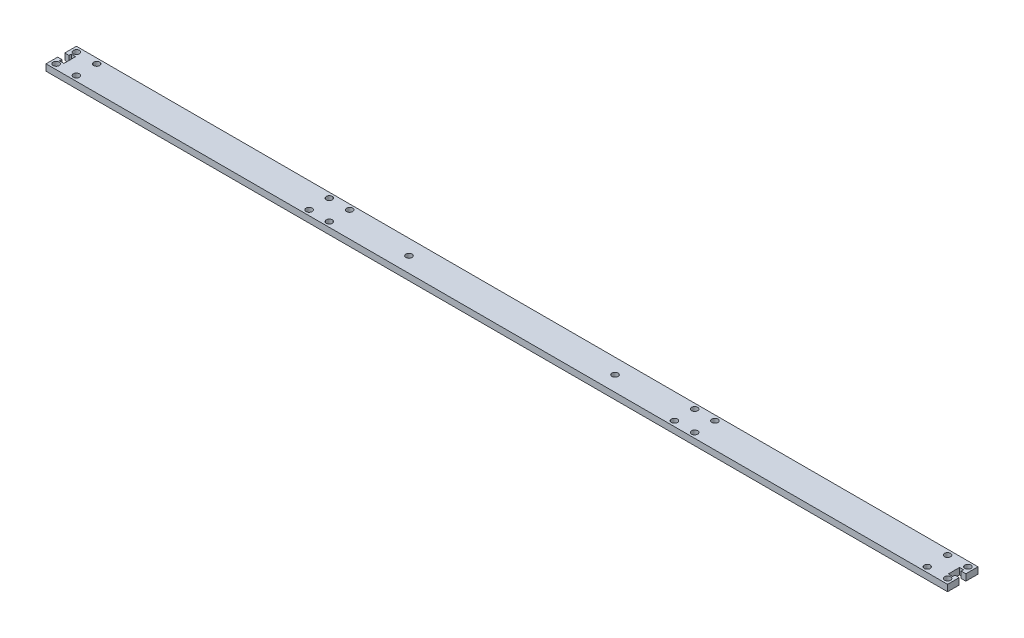
SolidWorks part; units mm, degrees
ref_plane "Front Plane" through (0, 0, 0) normal (0, 0, 1) x (1, 0, 0)
ref_plane "Top Plane" through (0, 0, 0) normal (0, 1, 0) x (1, 0, 0)
ref_plane "Right Plane" through (0, 0, 0) normal (1, 0, 0) x (0, 0, -1)
sketch "Sketch1" plane through (0, 0, 0) normal (0, 1, 0) x (1, 0, 0)
  line L0 (139.7, 7.5) -> (132.2, 7.5)
  line L1 (0, 0) -> (139.7, 0)
  line L2 (0, 0) -> (0, 15)
  line L3 (0, 15) -> (139.7, 15)
  line L4 (139.7, 0) -> (139.7, 15)
  line L5 (0, 7.5) -> (7.5, 7.5)
  line L6 (7.5, 7.5) -> (7.5, 12.5)
  line L7 (7.5, 12.5) -> (2.5, 12.5)
  line L8 (7.5, 12.5) -> (12.5, 12.5)
  line L9 (7.5, 7.5) -> (7.5, 2.5)
  line L10 (7.5, 2.5) -> (2.5, 2.5)
  line L11 (7.5, 2.5) -> (12.5, 2.5)
  line L12 (69.85, 0) -> (69.85, 15)
  line L13 (139.7, 0) -> (139.7, 15)
  line L14 (139.7, 0) -> (304.8, 0)
  line L15 (139.7, 15) -> (304.8, 15)
  line L16 (222.25, 0) -> (222.25, 15)
  line L17 (304.8, 0) -> (304.8, 15)
  line L18 (444.5, 15) -> (304.8, 15)
  line L19 (304.8, 0) -> (304.8, 15)
  line L20 (444.5, 0) -> (304.8, 0)
  line L21 (444.5, 0) -> (444.5, 15)
  line L22 (222.25, 7.5) -> (273.05, 7.5)
  line L23 (222.25, 7.5) -> (171.45, 7.5)
  circle A0 centre (2.5, 2.5) radius 1.5
  circle A1 centre (2.5, 12.5) radius 1.5
  circle A2 centre (12.5, 12.5) radius 1.5
  circle A3 centre (12.5, 2.5) radius 1.5
  circle A4 centre (137.2, 12.5) radius 1.5
  circle A5 centre (127.2, 12.5) radius 1.5
  circle A6 centre (137.2, 2.5) radius 1.5
  circle A7 centre (127.2, 2.5) radius 1.5
  circle A8 centre (432, 12.5) radius 1.5
  circle A9 centre (442, 12.5) radius 1.5
  circle A10 centre (442, 2.5) radius 1.5
  circle A11 centre (432, 2.5) radius 1.5
  circle A12 centre (307.3, 12.5) radius 1.5
  circle A13 centre (317.3, 12.5) radius 1.5
  circle A14 centre (317.3, 2.5) radius 1.5
  circle A15 centre (307.3, 2.5) radius 1.5
  circle A16 centre (273.05, 7.5) radius 1.5
  circle A17 centre (171.45, 7.5) radius 1.5
  dimension "D11" = 82.55
  dimension "D12" = 50.8
  dimension "D1" = 15
  dimension "D2" = 139.7
  dimension "D3" = 7.5
  dimension "D4" = 7.5
  dimension "D5" = 5
  dimension "D6" = 5
  dimension "D7" = 5
  dimension "D8" = 5
  dimension "D9" = 5
  dimension "D10" = 5
  dimension "D13" = 50.8
extrude "Boss-Extrude1" add sketch "Sketch1" along normal blind 3.175 contours A3 A0 L2 L1 L12 L3 A1 A2 | L12 L1 L4 L3 A6 A4 A5 A7 | L14 L16 L15 L4 | L14 L17 L15 L16 | L20 L21 L18 L17 A15 A14 A13 A12 A10 A8 A9 A11 region at (35.6856, 0, -7.5) region at (104.0144, 0, -7.5) region at (140.539, 0, -3.75) region at (223.089, 0, -3.75) region at (374.65, 0, -7.5)
sketch "Sketch4" plane through (0, 3.175, 0) normal (0, 1, 0) x (1, 0, 0)
  line L0 (444.5, 7.5) -> (432.4339, 7.5)
  line L1 (444.5, 0) -> (444.5, 15) construction
  line L2 (0, 15) -> (444.5, 15) construction
  line L3 (222.25, 15) -> (222.25, 0)
  line L4 (0, 0) -> (444.5, 0) construction
  line L5 (444.5, 9) -> (442.2, 9)
  line L6 (442.2, 9) -> (442.2, 10.15)
  line L7 (442.2, 10.15) -> (440.5, 10.15)
  line L8 (440.5, 10.15) -> (440.5, 7.5)
  line L9 (444.5, 9.25) -> (442.45, 9.25)
  line L10 (442.45, 9.25) -> (442.45, 10.4)
  line L11 (442.45, 10.4) -> (440.25, 10.4)
  line L12 (440.25, 10.4) -> (440.25, 7.5)
  line L13 (444.5, 5.75) -> (442.45, 5.75)
  line L14 (442.45, 5.75) -> (442.45, 4.6)
  line L15 (442.45, 4.6) -> (440.25, 4.6)
  line L16 (440.25, 4.6) -> (440.25, 7.5)
  line L17 (0, 9.25) -> (2.05, 9.25)
  line L18 (2.05, 9.25) -> (2.05, 10.4)
  line L19 (0, 5.75) -> (2.05, 5.75)
  line L20 (2.05, 5.75) -> (2.05, 4.6)
  line L21 (2.05, 4.6) -> (4.25, 4.6)
  line L22 (4.25, 4.6) -> (4.25, 7.5)
  line L23 (4.25, 10.4) -> (4.25, 7.5)
  line L24 (2.05, 10.4) -> (4.25, 10.4)
  line L25 (0, 9.25) -> (0, 5.75)
  line L26 (444.5, 9.25) -> (444.5, 5.75)
  line M20 (0, 15) -> (0, 0)
  line M22 (444.5, 0) -> (444.5, 15)
  dimension "D1" = 1.5
  dimension "D2" = 1.15
  dimension "D3" = 1.7
  dimension "D4" = 2.65
  dimension "D5" = 2.3
  dimension "D6" = 0.25
extrude "Cut-Extrude2" cut sketch "Sketch4" against normal blind 10 contours L16 L15 L14 L13 L0 M22 | L7 L8 L0 L5 L6 M22 | L24 L18 L17 L19 L20 L21 L22 L23 M20 region at (442.1148, 3.175, -6.257) region at (442.2174, 3.175, -8.5756) region at (2.3852, 3.175, -7.5)
sketch "Sketch6" plane through (440.5, 0, 0) normal (1, 0, 0) x (0, 0, -1)
  line L0 (10.15, 0) -> (7.5, 0) construction
  line L5 (7.5, 3.175) -> (10.15, 3.175)
  line L6 (7.5, 3.175) -> (7.5, 0)
  line L7 (7.5, 0) -> (10.15, 0)
  line L8 (10.15, 3.175) -> (10.15, 0)
extrude "Cut-Extrude3" cut sketch "Sketch6" against normal blind 0.25
